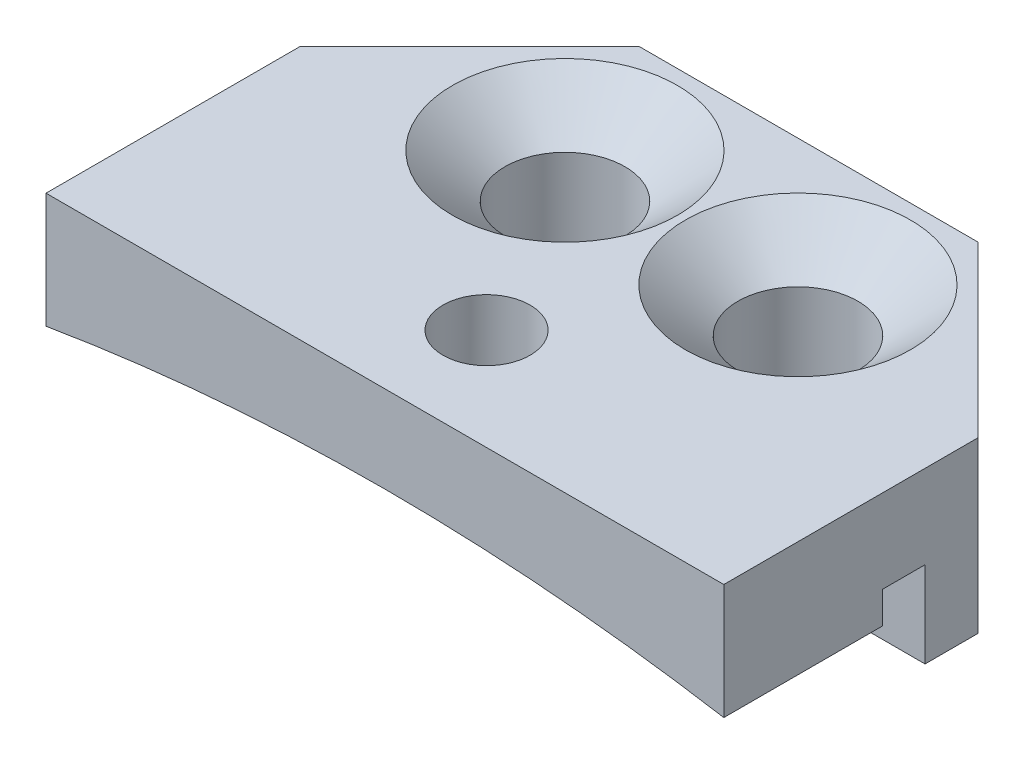
SolidWorks part; units mm, degrees
ref_plane "Front Plane" through (0, 0, 0) normal (0, 0, 1) x (1, 0, 0)
ref_plane "Top Plane" through (0, 0, 0) normal (0, 1, 0) x (1, 0, 0)
ref_plane "Right Plane" through (0, 0, 0) normal (1, 0, 0) x (0, 0, -1)
sketch "Sketch1" plane through (0, 0, 0) normal (0, 1, 0) x (1, 0, 0)
  line L0 (-12.7, 7.9375) -> (12.7, -7.9375) construction
  line L1 (-12.7, 7.9375) -> (12.7, 7.9375)
  line L2 (-12.7, 7.9375) -> (-12.7, -7.9375)
  line L3 (-12.7, -7.9375) -> (12.7, -7.9375)
  line L4 (12.7, 7.9375) -> (12.7, -7.9375)
  point P4 (0, 0)
  dimension "D1" = 15.875
  dimension "D2" = 25.4
extrude "Boss-Extrude1" add sketch "Sketch1" along normal blind 6.35
chamfer "Chamfer1" distance 6.35 angle 45 2 edges at (12.7, 3.175, -7.9375) (-12.7, 3.175, -7.9375)
sketch "Sketch2" plane through (0, 0, 7.9375) normal (0, 0, 1) x (1, 0, 0)
  line L0 (-2.7178, 3.048) -> (-2.7178, 0) construction
  line L1 (-2.7178, 0) -> (2.7178, 0) construction
  line L2 (2.7178, 3.048) -> (2.7178, 0) construction
  line L3 (-12.7, 0) -> (12.7, 0) construction
  line L4 (-12.7, 2.0307) -> (12.7, 2.0307) construction
  line L5 (-12.7, 2.0307) -> (-12.7, 0)
  line L6 (-12.7, 0) -> (12.7, 0)
  line L7 (12.7, 0) -> (12.7, 2.0307)
  arc A0 (-12.7, 2.0307) -> (12.7, 2.0307) centre (0, -73.1035) cw
  point P7 (0, 0)
  point P12 (0, 0)
  dimension "D2" = 76.2
  dimension "D1" = 5.4356
  dimension "D3" = 25.4
  dimension "D4" = 3.048
extrude "Cut-Extrude1" cut sketch "Sketch2" against normal blind 6.7469
sketch "Sketch3" plane through (0, 6.35, 0) normal (0, 1, 0) x (1, 0, 0)
  circle A0 centre (0, -4.1293) radius 1.6319 construction
  circle A1 centre (0, -4.1293) radius 1.6319
extrude "Cut-Extrude2" cut sketch "Sketch3" against normal through all
hole_wizard "CSK for #8 Flat Head Machine Screw (100)1" positions "Sketch4" profile "Sketch5" countersink size "#8" standard "ANSI Inch" end condition through all
sketch "Sketch4" plane through (0, 6.35, 0) normal (0, 1, 0) x (1, 0, 0)
  line L0 (0, 7.9375) -> (0, -1.7163) construction
  line L2 (6.35, 7.9375) -> (-6.35, 7.9375) construction
  point P2 (-4.3656, 3.175)
  point P24 (4.3656, 3.175)
  dimension "D2" = 4.7625
  dimension "D1" = 4.3656
sketch "Sketch5" plane through (-4.3656, 6.35, -3.175) normal (1, 0, 0) x (0, 0, 1)
  line L0 (0, 0) -> (0, 6.35)
  line L1 (0, 6.35) -> (2.2479, 6.35)
  line L2 (2.2479, 6.35) -> (2.2479, 1.6518)
  line L3 (2.2479, 1.6518) -> (4.2164, 0)
  line L5 (4.2164, 0) -> (0, 0)
  line L6 (-2.2479, 1.6518) -> (-4.2164, 0) construction
  line L11 (0, -6.35) -> (0, 107.95) construction
  dimension "Thru Hole Dia." = 4.4958
  dimension "Thru Hole Depth" = 6.35
  dimension "Near C'Sink Dia." = 8.4328
  dimension "Near C'Sink Angle" = 100
sketch "Sketch6" plane through (12.7, 0, 0) normal (1, 0, 0) x (0, 0, -1)
  line L0 (-1.1906, 2.0307) -> (-7.9375, 2.0307) construction
  line L1 (-1.9844, 3.2213) -> (-0.3969, 3.2213)
  line L2 (-1.9844, 3.2213) -> (-1.9844, 0)
  line L3 (-1.9844, 0) -> (-0.3969, 0)
  line L4 (-0.3969, 3.2213) -> (-0.3969, 0)
  point P4 (-1.1906, 0)
  dimension "D1" = 1.1906
  dimension "D2" = 1.5875
extrude "Cut-Extrude3" cut sketch "Sketch6" against normal through all
